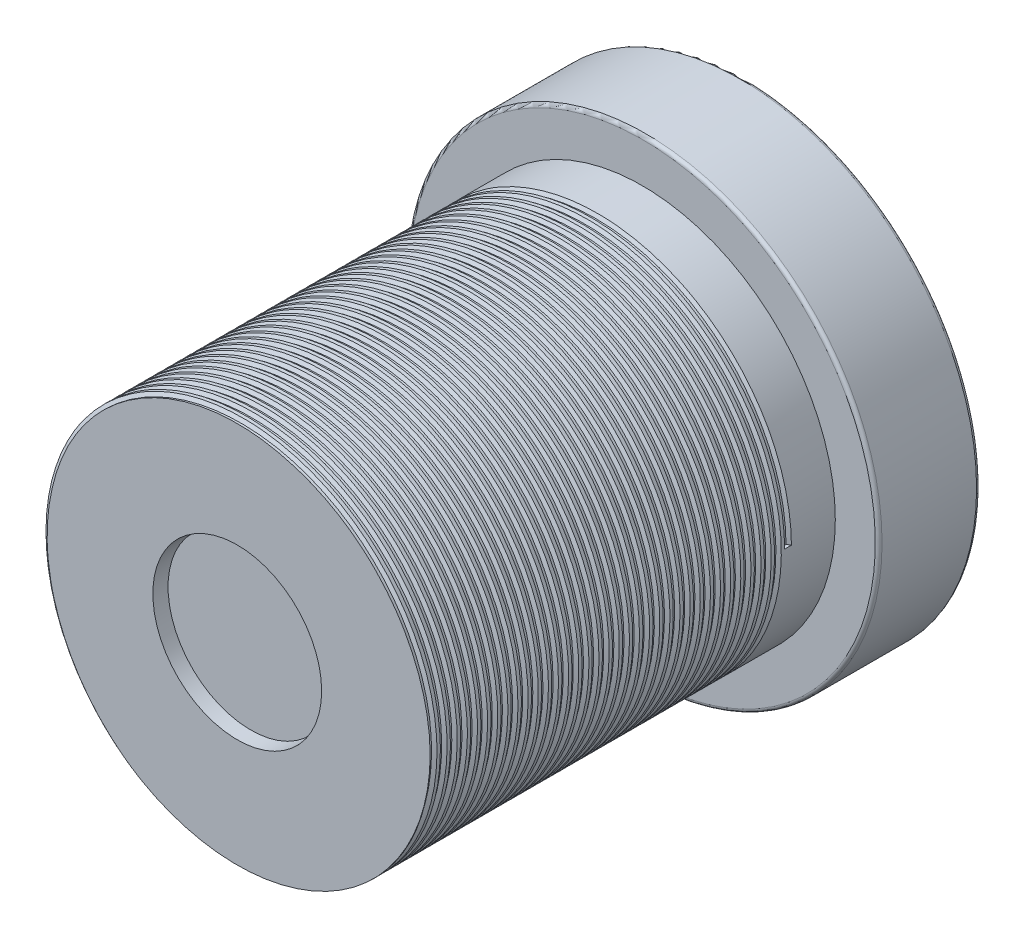
SolidWorks part; units mm, degrees
ref_plane "前视基准面" through (0, 0, 0) normal (0, 0, 1) x (1, 0, 0)
ref_plane "上视基准面" through (0, 0, 0) normal (0, 1, 0) x (1, 0, 0)
ref_plane "右视基准面" through (0, 0, 0) normal (1, 0, 0) x (0, 0, -1)
sketch "草图1" plane through (0, 0, 0) normal (0, 0, 1) x (1, 0, 0)
  circle A0 centre (0, 0) radius 5.715
  circle A1 centre (0, 0) radius 2.5
  dimension "D1" = 11.43
  dimension "D2" = 5
extrude "凸台-拉伸1" add sketch "草图1" along normal blind 12
ref_plane "基准面1" through (0, 0, 11.5) normal (0, 0, 1) x (1, 0, 0)
sketch "草图2" plane through (0, 0, 11.5) normal (0, 0, 1) x (1, 0, 0)
  circle A1 centre (0, 0) radius 2.45
  dimension "D1" = 4.9
extrude "凸台-拉伸2" add sketch "草图2" along normal blind 0.1 separate body
sketch "草图3" plane through (0, 0, 0) normal (0, 0, -1) x (-1, 0, 0)
  circle A0 centre (0, 0) radius 7
  circle A1 centre (0, 0) radius 4
  dimension "D1" = 14
  dimension "D2" = 8
extrude "凸台-拉伸3" add sketch "草图3" along normal blind 3
ref_plane "基准面2" through (0, 0, -1.5) normal (0, 0, -1) x (-1, 0, 0)
chamfer "倒角1" distance 1.5 angle 30 1 edges at (-4, 0, -3)
sketch "草图4" plane through (0, 0, -1.5) normal (0, 0, -1) x (-1, 0, 0)
  circle A0 centre (0, 0) radius 3.95
  dimension "D1" = 7.9
extrude "凸台-拉伸4" add sketch "草图4" along normal blind 0.1 separate body
sketch "草图5" plane through (0, 0, 12) normal (0, 0, 1) x (1, 0, 0)
  circle A0 centre (0, 0) radius 5.715
curve "螺旋线/涡状线1" pitch 0.3 height 10.5 turns 35
sketch "草图6" plane through (0, 0, 0) normal (0, 1, 0) x (1, 0, 0)
  line L0 (5.715, -12) -> (5.715, -11.8)
  line L1 (5.715, -12) -> (5.715, 0) construction
  line L2 (5.715, -11.8) -> (5.615, -11.86)
  line L3 (5.615, -11.86) -> (5.615, -11.94)
  line L4 (5.615, -11.94) -> (5.715, -12)
  line L5 (-5.715, -12) -> (5.715, -12) construction
  dimension "D1" = 0.2
  dimension "D2" = 0.1
  dimension "D3" = 0.08
sweep "切除-扫描1" cut profiles "草图6" path "螺旋线/涡状线1"
fillet "圆角1" radius 0.1 2 edges at (-7, 0, 0) (-7, 0, -3)
